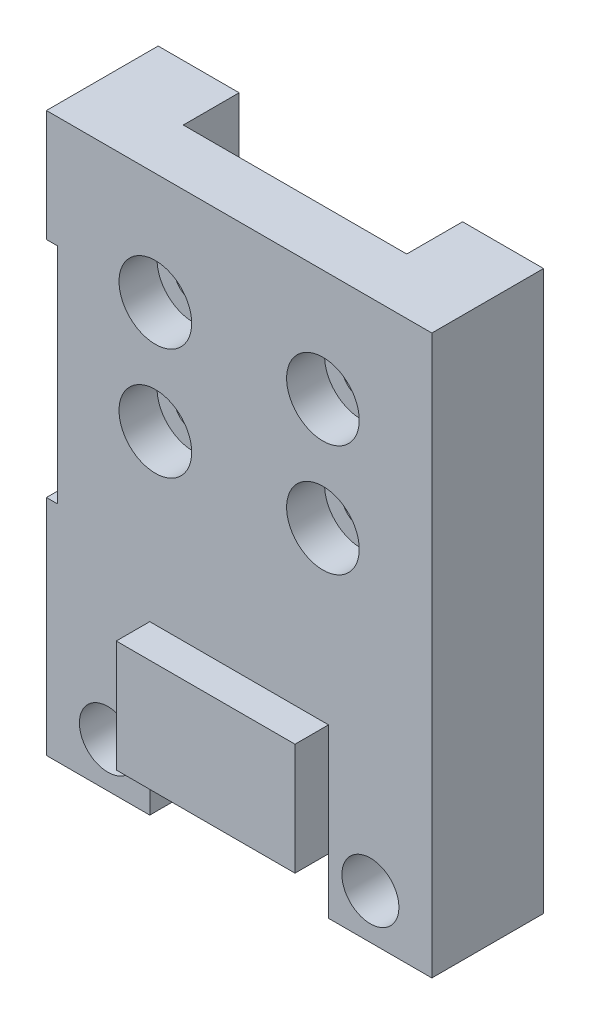
SolidWorks part; units mm, degrees
ref_plane "前视基准面" through (0, 0, 0) normal (0, 0, 1) x (1, 0, 0)
ref_plane "上视基准面" through (0, 0, 0) normal (0, 1, 0) x (1, 0, 0)
ref_plane "右视基准面" through (0, 0, 0) normal (1, 0, 0) x (0, 0, -1)
sketch "草图1" plane through (0, 0, 0) normal (0, 0, 1) x (1, 0, 0)
  line L1 (0, 0) -> (34.5, 0)
  line L2 (0, 0) -> (0, 50)
  line L3 (0, 50) -> (34.5, 50)
  line L4 (34.5, 0) -> (34.5, 50)
  dimension "D1" = 50
  dimension "D2" = 34.5
extrude "凸台-拉伸1" add sketch "草图1" along normal blind 10
sketch "草图2" plane through (0, 50, 0) normal (0, 1, 0) x (1, 0, 0)
  line L0 (17.25, 0) -> (17.25, -12.5244) construction
  line L1 (34.5, 0) -> (0, 0) construction
  line L3 (7.25, 0) -> (27.25, 0)
  line L4 (7.25, 0) -> (7.25, -5)
  line L5 (7.25, -5) -> (27.25, -5)
  line L6 (27.25, 0) -> (27.25, -5)
  dimension "D1" = 20
  dimension "D2" = 5
extrude "切除-拉伸1" cut sketch "草图2" against normal through all
sketch "草图3" plane through (0, 0, 10) normal (0, 0, 1) x (1, 0, 0)
  line L0 (17.25, 0) -> (17.25, 36.3385) construction
  line L1 (0, 0) -> (34.5, 0) construction
  line L2 (34.5, 50) -> (0, 50) construction
  line L3 (9.25, 0) -> (25.25, 0)
  line L4 (9.25, 0) -> (9.25, 5)
  line L5 (9.25, 5) -> (25.25, 5)
  line L6 (25.25, 0) -> (25.25, 5)
  dimension "D1" = 16
  dimension "D2" = 45
extrude "切除-拉伸2" cut sketch "草图3" against normal blind 10
sketch "草图4" plane through (0, 0, 10) normal (0, 0, 1) x (1, 0, 0)
  line L0 (17.25, 5) -> (17.25, 23.9863) construction
  line L1 (25.25, 5) -> (9.25, 5) construction
  line L2 (34.5, 50) -> (0, 50) construction
  circle A0 centre (5.5, 4) radius 2.55
  circle A1 centre (29, 4) radius 2.55
  dimension "D2" = 5.1
  dimension "D1" = 46
  dimension "D3" = 23.5
extrude "切除-拉伸3" cut sketch "草图4" against normal blind 4
hole_wizard "M4 螺纹孔1" positions "草图5" profile "草图6" tap size "M4" standard "ISO"
sketch "草图5" plane through (0, 5, 0) normal (0, -1, 0) x (-1, 0, 0)
  line L0 (-17.25, -10) -> (-17.25, -5) construction
  line L1 (-25.25, -10) -> (-9.25, -10) construction
  line L2 (-25.25, -5) -> (-9.25, -5) construction
  line L4 (-27.25, 0) -> (-34.5, 0) construction
  point P0 (-12.5, -8)
  point P2 (-22, -8)
  point P12 (0, 0)
  point P15 (-30.875, 0)
  dimension "D1" = 8
  dimension "D2" = 9.5
sketch "草图6" plane through (12.5, 5, 8) normal (1, 0, 0) x (0, 0, -1)
  line L0 (0, 0) -> (0, 11.0914)
  line L1 (0, 11.0914) -> (1.65, 10.1)
  line L2 (1.65, 10.1) -> (1.65, 0)
  line L5 (1.65, 0) -> (0, 0)
  line L10 (0, 11.0914) -> (-1.65, 10.1) construction
  line L11 (0, -6.35) -> (0, 107.95) construction
  dimension "螺纹孔钻头直径" = 3.3
  dimension "螺纹孔钻头深度" = 10.1
  dimension "导头角度" = 118
cosmetic thread "孔螺蚊线1" parameters "D1"=8, "D2"=4
cosmetic thread "孔螺蚊线2" parameters "D1"=8, "D2"=4
sketch "草图7" plane through (0, 0, 10) normal (0, 0, 1) x (1, 0, 0)
  line L0 (0, 0) -> (9.25, 0) construction
  line L1 (25.25, 5) -> (9.25, 5)
  line L2 (25.25, 5) -> (25.25, 15)
  line L3 (25.25, 15) -> (9.25, 15)
  line L4 (9.25, 5) -> (9.25, 15)
  dimension "D1" = 16
  dimension "D2" = 15
extrude "凸台-拉伸2" add sketch "草图7" along normal blind 3
sketch "草图8" plane through (0, 0, 0) normal (-1, 0, 0) x (0, 0, 1)
  line L0 (10, 50) -> (10, 0) construction
  line L1 (10, 40) -> (0, 40)
  line L2 (10, 40) -> (10, 20)
  line L3 (10, 20) -> (0, 20)
  line L4 (0, 40) -> (0, 20)
  line L5 (0, 50) -> (0, 0) construction
  line L6 (10, 50) -> (0, 50) construction
  dimension "D1" = 10
  dimension "D2" = 20
extrude "切除-拉伸4" cut sketch "草图8" against normal blind 1
hole_wizard "M4 螺纹孔2" positions "草图9" profile "草图10" tap size "M4" standard "ISO"
sketch "草图9" plane through (1, 0, 0) normal (-1, 0, 0) x (0, 0, 1)
  line L0 (5, 40) -> (5, 14.5498) construction
  line L1 (10, 40) -> (0, 40) construction
  line L3 (10, 0) -> (0, 0) construction
  point P0 (5, 35)
  point P2 (5, 25)
  point P10 (0, 0)
  point P11 (0, 0)
  point P14 (0, 0)
  dimension "D1" = 25
  dimension "D2" = 35
sketch "草图10" plane through (1, 35, 5) normal (0, 1, 0) x (0, 0, 1)
  line L0 (0, 0) -> (0, 11.0914)
  line L1 (0, 11.0914) -> (1.65, 10.1)
  line L2 (1.65, 10.1) -> (1.65, 0)
  line L5 (1.65, 0) -> (0, 0)
  line L10 (0, 11.0914) -> (-1.65, 10.1) construction
  line L11 (0, -6.35) -> (0, 107.95) construction
  dimension "螺纹孔钻头直径" = 3.3
  dimension "螺纹孔钻头深度" = 10.1
  dimension "导头角度" = 118
cosmetic thread "孔螺蚊线3" parameters "D1"=8, "D2"=4
cosmetic thread "孔螺蚊线4" parameters "D1"=8, "D2"=4
hole_wizard "M3 六角凹头螺钉的柱形沉头孔1" positions "草图11" profile "草图12" counterbore size "M3" standard "ISO"
sketch "草图11" plane through (0, 0, 10) normal (0, 0, 1) x (1, 0, 0)
  line L0 (17.25, 50) -> (17.25, 15) construction
  line L1 (34.5, 50) -> (0, 50) construction
  line L2 (25.25, 15) -> (9.25, 15) construction
  point P0 (9.75, 40)
  point P2 (9.75, 30)
  point P13 (24.75, 30)
  point P14 (24.75, 40)
  point P15 (0, 0)
  point P16 (0, 0)
  dimension "D1" = 15
  dimension "D2" = 10
  dimension "D3" = 10
sketch "草图12" plane through (9.75, 40, 10) normal (1, 0, 0) x (0, -1, 0)
  line L0 (0, 0) -> (0, 11.1215)
  line L1 (0, 11.1215) -> (1.7, 10.1)
  line L2 (1.7, 10.1) -> (1.7, 3.4)
  line L3 (1.7, 3.4) -> (3.25, 3.4)
  line L4 (3.25, 3.4) -> (3.25, 0)
  line L5 (3.25, 0) -> (0, 0)
  line L10 (0, 11.1215) -> (-1.7, 10.1) construction
  line L11 (0, -6.35) -> (0, 107.95) construction
  dimension "孔直径" = 3.4
  dimension "孔深度" = 10.1
  dimension "柱形沉头孔直径" = 6.5
  dimension "柱形沉头孔深度" = 3.4
  dimension "导头角度" = 118
